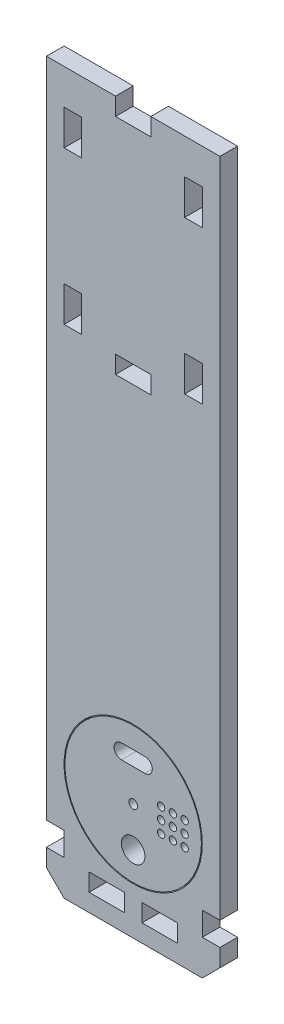
SolidWorks part; units mm, degrees
ref_plane "Front Plane" through (0, 0, 0) normal (0, 0, 1) x (1, 0, 0)
ref_plane "Top Plane" through (0, 0, 0) normal (0, 1, 0) x (1, 0, 0)
ref_plane "Right Plane" through (0, 0, 0) normal (1, 0, 0) x (0, 0, -1)
sketch "Sketch2" plane through (0, 0, 0) normal (0, 1, 0) x (1, 0, 0)
  line L0 (0, 0) -> (0, 6) construction
  dimension "D1" = 6
sketch "Sketch1" plane through (0, 0, 0) normal (0, 0, 1) x (1, 0, 0)
  line L0 (0, 33.5) -> (0, 20) construction
  line L1 (-29.5, 0) -> (29.5, 0)
  line L2 (-29.5, 0) -> (-29.5, 239)
  line L3 (-29.5, 239) -> (29.5, 239)
  line L4 (29.5, 0) -> (29.5, 239)
  line L5 (0, 10) -> (0, 16) construction
  line L6 (0, 10) -> (0, 6) construction
  line L7 (-23.5, 33.5) -> (-29.5, 33.5) construction
  line L8 (-29.5, 163) -> (29.5, 163) construction
  line L9 (-23.5, 157) -> (-23.5, 233) construction
  line L10 (-29.5, 233) -> (29.5, 233) construction
  line L11 (29.5, 6) -> (-29.5, 6) construction
  line L12 (0, 6) -> (0, 0) construction
  line L13 (0, 163) -> (0, 157) construction
  line L14 (0, 233) -> (0, 239) construction
  line L15 (-29.5, 223) -> (29.5, 223) construction
  line L16 (23.5, 157) -> (23.5, 233) construction
  line L21 (-21, 157) -> (21, 157) construction
  line L22 (0, 33.5) -> (13.5, 33.5) construction
  line L24 (9.5, 29.5) -> (17.5, 29.5) construction
  line L25 (9.5, 29.5) -> (9.5, 37.5) construction
  line L26 (9.5, 37.5) -> (17.5, 37.5) construction
  line L27 (17.5, 29.5) -> (17.5, 37.5) construction
  line L28 (9.5, 29.5) -> (17.5, 37.5) construction
  line L29 (9.5, 37.5) -> (17.5, 29.5) construction
  line L30 (0, 33.5) -> (0, 47) construction
  line L31 (-4, 47) -> (4, 47) construction
  line L32 (-4, 49.5) -> (4, 49.5)
  line L33 (-4, 44.5) -> (4, 44.5)
  line L34 (-21, 157) -> (-23.5, 157) construction
  line L35 (21, 157) -> (23.5, 157) construction
  line L36 (21, 157) -> (21, 6) construction
  line L37 (21, 6) -> (23.5, 6) construction
  line L38 (23.5, 6) -> (23.5, 157) construction
  line L39 (-23.5, 157) -> (-23.5, 6) construction
  line L40 (-21, 157) -> (-21, 6) construction
  circle A0 centre (0, 33.5) radius 23.5
  circle A1 centre (0, 20) radius 4
  circle A2 centre (0, 33.5) radius 23.2
  circle A5 centre (9.5, 29.5) radius 1.25
  circle A6 centre (13.5, 29.5) radius 1.25
  circle A7 centre (17.5, 29.5) radius 1.25
  circle A8 centre (13.5, 33.5) radius 1.25
  circle A9 centre (17.5, 33.5) radius 1.25
  circle A10 centre (17.5, 37.5) radius 1.25
  circle A11 centre (13.5, 37.5) radius 1.25
  circle A12 centre (9.5, 37.5) radius 1.25
  circle A13 centre (9.5, 33.5) radius 1.25
  arc A14 (-4, 49.5) -> (-4, 44.5) centre (-4, 47) ccw
  arc A15 (4, 44.5) -> (4, 49.5) centre (4, 47) ccw
  circle A16 centre (0, 33.5) radius 1.5
  point P35 (0, 157)
  point P57 (0, 47)
  dimension "D4" = 8
  dimension "D13" = 2.5
  dimension "D18" = 3
  dimension "D1" = 59
  dimension "D2" = 239
  dimension "D3" = 6
  dimension "D5" = 20
  dimension "D6" = 6
  dimension "D7" = 0.3
  dimension "D8" = 6
  dimension "D10" = 60
  dimension "D11" = 10
  dimension "D12" = 8
  dimension "D14" = 8
  dimension "D15" = 5
  dimension "D16" = 42
  dimension "D17" = 2.5
  dimension "D9" = 151
extrude "Boss-Extrude1" add sketch "Sketch1" against normal up to vertex (6 mm away) contours L1 L4 L3 L2 A0 | A2 A15 L33 A14 L32 A13 A12 A11 A10 A9 A8 A7 A6 A5 A1 region at (0, 131.5657, 0) region at (-22.5438, 33.5, 0) up to point (0, 0, -6)
sketch "Sketch3" plane through (0, 0, 0) normal (0, 0, 1) x (1, 0, 0)
  line L0 (0, 233) -> (0, 239) construction
  line L1 (-6, 233) -> (6, 233)
  line L2 (-6, 233) -> (-6, 239)
  line L3 (-6, 239) -> (6, 239)
  line L4 (6, 233) -> (6, 239)
  line L5 (-6, 233) -> (6, 239) construction
  line L6 (-6, 239) -> (6, 233) construction
  line L7 (-29.5, 239) -> (29.5, 239) construction
  line L8 (-6, 233) -> (-29.5, 233)
  line L9 (6, 233) -> (29.5, 233)
  line L10 (0, 163) -> (0, 157) construction
  line L11 (-6, 157) -> (6, 157)
  line L12 (-6, 157) -> (-6, 163)
  line L13 (-6, 163) -> (6, 163)
  line L14 (6, 157) -> (6, 163)
  line L15 (-6, 157) -> (6, 163) construction
  line L16 (-6, 163) -> (6, 157) construction
  line L17 (-29.5, 163) -> (29.5, 163) construction
  line L18 (-23.5, 157) -> (-23.5, 233) construction
  line L19 (-23.5, 175) -> (-17.5, 175)
  line L20 (-23.5, 175) -> (-23.5, 163)
  line L21 (-23.5, 163) -> (-17.5, 163)
  line L22 (-17.5, 175) -> (-17.5, 163)
  line L23 (23.5, 157) -> (23.5, 233) construction
  line L24 (23.5, 175) -> (17.5, 175)
  line L25 (23.5, 175) -> (23.5, 163)
  line L26 (23.5, 163) -> (17.5, 163)
  line L27 (17.5, 175) -> (17.5, 163)
  line L28 (-17.5, 227) -> (-17.5, 233) construction
  line L29 (-23.5, 227) -> (-17.5, 227)
  line L30 (-23.5, 227) -> (-23.5, 215)
  line L31 (-23.5, 215) -> (-17.5, 215)
  line L32 (-17.5, 227) -> (-17.5, 215)
  line L33 (23.5, 227) -> (17.5, 227)
  line L34 (23.5, 227) -> (23.5, 215)
  line L35 (23.5, 215) -> (17.5, 215)
  line L36 (17.5, 227) -> (17.5, 215)
  line L37 (0, 6) -> (0, 0) construction
  line L38 (-3, 0) -> (3, 0)
  line L39 (-3, 0) -> (-3, 6)
  line L40 (-3, 6) -> (3, 6)
  line L41 (3, 0) -> (3, 6)
  line L42 (-3, 0) -> (3, 6) construction
  line L43 (-3, 6) -> (3, 0) construction
  line L44 (29.5, 6) -> (-29.5, 6) construction
  line L45 (-29.5, 0) -> (-29.5, 239) construction
  line L46 (-23.5, 6) -> (-29.5, 6)
  line L47 (-23.5, 6) -> (-23.5, 14)
  line L48 (-23.5, 14) -> (-29.5, 14)
  line L49 (-29.5, 6) -> (-29.5, 14)
  line L50 (29.5, 0) -> (29.5, 239) construction
  line L51 (23.5, 6) -> (29.5, 6)
  line L52 (23.5, 6) -> (23.5, 14)
  line L53 (23.5, 14) -> (29.5, 14)
  line L54 (29.5, 6) -> (29.5, 14)
  line L55 (-29.5, 0) -> (29.5, 0) construction
  line L56 (-3, 6) -> (-15, 6)
  line L57 (-3, 6) -> (-3, 0)
  line L58 (-3, 0) -> (-15, 0)
  line L59 (-15, 6) -> (-15, 0)
  line L61 (3, 6) -> (15, 6)
  line L62 (3, 6) -> (3, 0)
  line L63 (3, 0) -> (15, 0)
  line L64 (15, 6) -> (15, 0)
  point P0 (0, 236)
  point P9 (0, 160)
  point P42 (0, 3)
  dimension "D3" = 6
  dimension "D2" = 12
  dimension "D5" = 8
  dimension "D4" = 6
  dimension "D6" = 12
  dimension "D1" = 12
  dimension "D7" = 12
extrude "Cut-Extrude1" cut sketch "Sketch3" against normal blind 10 contours L49 L46 L47 L48 | L51 L54 L53 L52 | L33 L36 L35 L34 | L24 L27 L26 L25 | L11 L14 L13 L12 | L22 L19 L20 L21 | L32 L29 L30 L31 | L1 L4 L3 L2 | L56 L59 L58 L39 | L64 L61 L41 L63 region at (0, 236, 0) region at (0, 160, 0) region at (-20.5, 169, 0) region at (20.5, 169, 0) region at (-20.5, 221, 0) region at (20.5, 221, 0) region at (-9, 3, 0) region at (9, 3, 0) region at (-26.5, 10, 0) region at (26.5, 10, 0)
sketch "Sketch5" plane through (0, 0, 0) normal (0, 0, 1) x (1, 0, 0)
  line L0 (-29.5, 0) -> (-23.5, 0)
  line L1 (-29.5, 0) -> (29.5, 0) construction
  line L2 (-23.5, 0) -> (23.5, 0)
  line L3 (23.5, 0) -> (29.5, 0)
  line L4 (29.5, 0) -> (23.5, -6)
  line L5 (23.5, -6) -> (-23.5, -6)
  line L6 (-23.5, -6) -> (-29.5, 0)
  line L7 (-23.5, -6) -> (-23.5, 0) construction
  line L8 (23.5, 0) -> (23.5, -6) construction
  dimension "D1" = 6
extrude "Boss-Extrude3" add sketch "Sketch5" against normal up to surface (6 mm away) up to face at (-20.5, 221, -6)
equation "\"t_wood\"= 6' Thickness of the wood"
equation "\"t_glass\"= 2.5'Thickness of glass panels"
equation "\"w_glass\"= 181"
equation "\"h_glass\"= 151"
equation "\"h_food_internal\" = 60"
equation "\"entry_height\"= 20"
equation "\"entry diameter\"= 8"
equation "\"glass_bottom_overlap\"= 8"
equation "\"default_finger_size\"= 12"
equation "\"brood_depth\"= 42"
equation "\"outer_box_depth\" = \"brood_depth\" + ( 2 * \"t_glass\" ) + ( 2 * \"t_wood\" )"
equation "\"outer_box_width\"= \"w_glass\" + ( 2 * \"t_wood\" )"
equation "\"food_top_clearance\"= 10"
equation "\"outer_box_height\"= \"t_wood\" + \"h_glass\" + \"t_wood\" + \"h_food_internal\" + \"food_top_clearance\" + \"t_wood\""
equation "\"food_internal_depth\"= \"brood_depth\" + \"t_glass\" + \"t_glass\" - \"t_wood\" - \"t_wood\""
equation "\"food_channel_clearance_width\"= 14"
equation "\"bar_top_play\"= 0.5"
equation "\"bar_entry_angle\"= 10"
equation "\"bar_width\"= 20"
equation "\"entry_disk_play\"= 0.3"
equation "\"D1@Sketch1\"=\"outer_box_depth\""
equation "\"D2@Sketch1\"=\"outer_box_height\""
equation "\"D3@Sketch1\"=\"t_wood\""
equation "\"D4@Sketch1\"=\"entry diameter\""
equation "\"D5@Sketch1\"=\"entry_height\""
equation "\"D6@Sketch1\"=\"t_wood\""
equation "\"D7@Sketch1\"=\"entry_disk_play\""
equation "\"D8@Sketch1\"=\"t_wood\""
equation "\"D10@Sketch1\"=\"h_food_internal\""
equation "\"D12@Sketch1\"=\"entry diameter\""
equation "\"D14@Sketch1\"=\"entry diameter\""
equation "\"D16@Sketch1\"=\"brood_depth\""
equation "\"D17@Sketch1\"=\"t_glass\""
equation "\"D9@Sketch1\"=\"h_glass\""
equation "\"D1@Sketch2\"=\"t_wood\""
equation "\"D2@Sketch3\"=\"default_finger_size\""
equation "\"D3@Sketch3\"=\"t_wood\""
equation "\"D5@Sketch3\"=\"glass_bottom_overlap\""
equation "\"D1@Sketch5\"=\"t_wood\""
equation "\"D4@Sketch3\"=\"t_wood\""
equation "\"D6@Sketch3\"=\"default_finger_size\""
equation "\"D1@Sketch3\"=\"default_finger_size\""
equation "\"D7@Sketch3\"=\"default_finger_size\""
